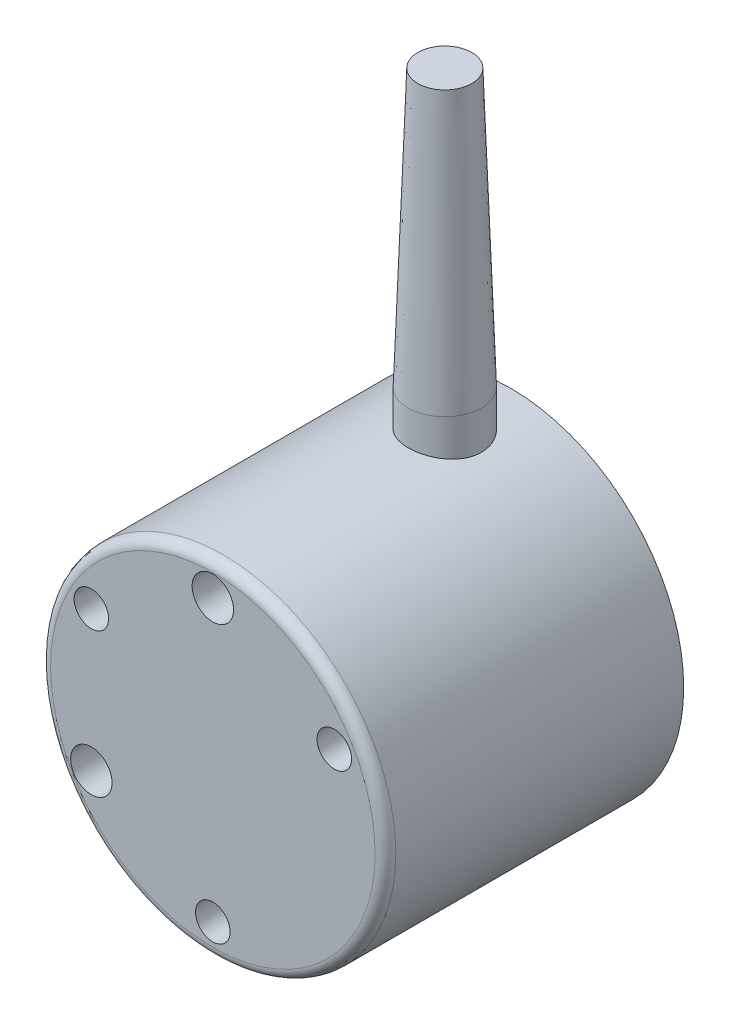
SolidWorks part; units mm, degrees
material "AISI 304"
ref_plane "Front Plane" through (0, 0, 0) normal (0, 0, 1) x (1, 0, 0)
ref_plane "Top Plane" through (0, 0, 0) normal (0, 1, 0) x (1, 0, 0)
ref_plane "Right Plane" through (0, 0, 0) normal (1, 0, 0) x (0, 0, -1)
ref_axis "Axis2" through (0, 0, -88.99) along (0, 0, 1)
ref_axis "Axis1" through (0, 55, 0) along (0, -1, 0)
ref_axis "Axis3" through (88.99, 0, 0) along (-1, 0, 0)
sketch "Sketch1" plane through (0, 0, 0) normal (0, 0, 1) x (1, 0, 0)
  circle A0 centre (0, 0) radius 12.5
  dimension "D1" = 25
extrude "Boss-Extrude1" add sketch "Sketch1" along normal blind 16.8 and the other way blind 4.8
hole_wizard "M3x0.5 Tapped Hole1" positions "Sketch3" profile "Sketch2" tap size "M3x0.5" standard "ANSI Metric"
sketch "Sketch3" plane through (0, 0, 16.8) normal (0, 0, 1) x (1, 0, 0)
  line L1 (0, 55) -> (0, -55) construction
  point P0 (0, -10.16)
  dimension "D1" = 10.16
sketch "Sketch2" plane through (0, -10.16, 16.8) normal (1, 0, 0) x (0, -1, 0)
  line L0 (0, 0) -> (0, 8.2511)
  line L1 (0, 8.2511) -> (1.25, 7.5)
  line L2 (1.25, 7.5) -> (1.25, 0)
  line L5 (1.25, 0) -> (0, 0)
  line L10 (0, 8.2511) -> (-1.25, 7.5) construction
  line L11 (0, -6.35) -> (0, 107.95) construction
  dimension "Tap Drill Dia." = 2.5
  dimension "Tap Drill Depth" = 7.5
  dimension "Drill Angle" = 118
cosmetic thread "Hole Thread1" parameters "D1"=6, "D2"=3
pattern_circular "CirPattern1" count 3 over 360 about axis through (0, 0, -88.99) along (0, 0, 1) of "M3x0.5 Tapped Hole1"
hole_wizard "Ø3.0mm Clearance Dowel Hole1" positions "Sketch5" profile "Sketch4" hole size "Ø3.0" standard "ANSI Metric"
sketch "Sketch5" plane through (0, 0, 16.8) normal (0, 0, 1) x (1, 0, 0)
  line L0 (0, 55) -> (0, -55) construction
  point P0 (-8.799, -5.08)
  point P2 (0, 10.16)
  dimension "D1" = 10.16
  dimension "D2" = 15.24
  dimension "D3" = 8.799
sketch "Sketch4" plane through (-8.799, -5.08, 16.8) normal (1, 0, 0) x (0, -1, 0)
  line L0 (0, 0) -> (0, 4.2013)
  line L1 (0, 4.2013) -> (1.5, 3.3)
  line L2 (1.5, 3.3) -> (1.5, 0)
  line L5 (1.5, 0) -> (0, 0)
  line L10 (0, 4.2013) -> (-1.5, 3.3) construction
  line L11 (0, -6.35) -> (0, 107.95) construction
  dimension "Hole Dia." = 3
  dimension "Hole Depth" = 3.3
  dimension "Drill Angle" = 118
hole_wizard "M3x0.5 Tapped Hole2" positions "Sketch7" profile "Sketch6" tap size "M3x0.5" standard "ANSI Metric"
sketch "Sketch7" plane through (0, 0, -4.8) normal (0, 0, -1) x (-1, 0, 0)
  line L0 (-88.99, 0) -> (88.99, 0) construction
  line L1 (0, 55) -> (0, -55) construction
  point P0 (10.16, 0)
  dimension "D1" = 10.16
sketch "Sketch6" plane through (-10.16, 0, -4.8) normal (1, 0, 0) x (0, 1, 0)
  line L0 (0, 0) -> (0, 8.2511)
  line L1 (0, 8.2511) -> (1.25, 7.5)
  line L2 (1.25, 7.5) -> (1.25, 0)
  line L5 (1.25, 0) -> (0, 0)
  line L10 (0, 8.2511) -> (-1.25, 7.5) construction
  line L11 (0, -6.35) -> (0, 107.95) construction
  dimension "Tap Drill Dia." = 2.5
  dimension "Tap Drill Depth" = 7.5
  dimension "Drill Angle" = 118
cosmetic thread "Hole Thread2" parameters "D1"=6, "D2"=3
pattern_circular "CirPattern2" count 3 over 360 about axis through (0, 0, -88.99) along (0, 0, 1) of "M3x0.5 Tapped Hole2"
hole_wizard "Ø3.0mm Clearance Dowel Hole2" positions "Sketch9" profile "Sketch8" hole size "Ø3.0" standard "ANSI Metric"
sketch "Sketch9" plane through (0, 0, -4.8) normal (0, 0, -1) x (-1, 0, 0)
  line L1 (0, 55) -> (0, -55) construction
  line L2 (-88.99, 0) -> (88.99, 0) construction
  point P0 (-9.208, -4.294)
  dimension "D1" = 9.208
  dimension "D2" = 4.294
sketch "Sketch8" plane through (9.208, -4.294, -4.8) normal (1, 0, 0) x (0, 1, 0)
  line L0 (0, 0) -> (0, 4.2013)
  line L1 (0, 4.2013) -> (1.5, 3.3)
  line L2 (1.5, 3.3) -> (1.5, 0)
  line L5 (1.5, 0) -> (0, 0)
  line L10 (0, 4.2013) -> (-1.5, 3.3) construction
  line L11 (0, -6.35) -> (0, 107.95) construction
  dimension "Hole Dia." = 3
  dimension "Hole Depth" = 3.3
  dimension "Drill Angle" = 118
sketch "Sketch10" plane through (0, 0, -4.8) normal (0, 0, -1) x (-1, 0, 0)
  circle A0 centre (0, 0) radius 3.0175
  dimension "D1" = 6.035
extrude "Cut-Extrude1" cut sketch "Sketch10" against normal blind 2.1
fillet "Fillet1" radius 0.75 1 edges at (12.5, 0, 16.8)
sketch "Sketch11" plane through (0, 0, 0) normal (0, 1, 0) x (1, 0, 0)
  circle A0 centre (0, 0) radius 2.65
  dimension "D1" = 5.3
extrude "Boss-Extrude2" add sketch "Sketch11" along normal blind 15
sketch "Sketch12" plane through (0, 15, 0) normal (0, 1, 0) x (1, 0, 0)
  circle A1 centre (0, 0) radius 2.65
  circle A2 centre (0, 0) radius 2.65
  dimension "D1" = 0
extrude "Boss-Extrude3" add sketch "Sketch12" along normal blind 20 draft 2
ref_point "sensor frame origin"
